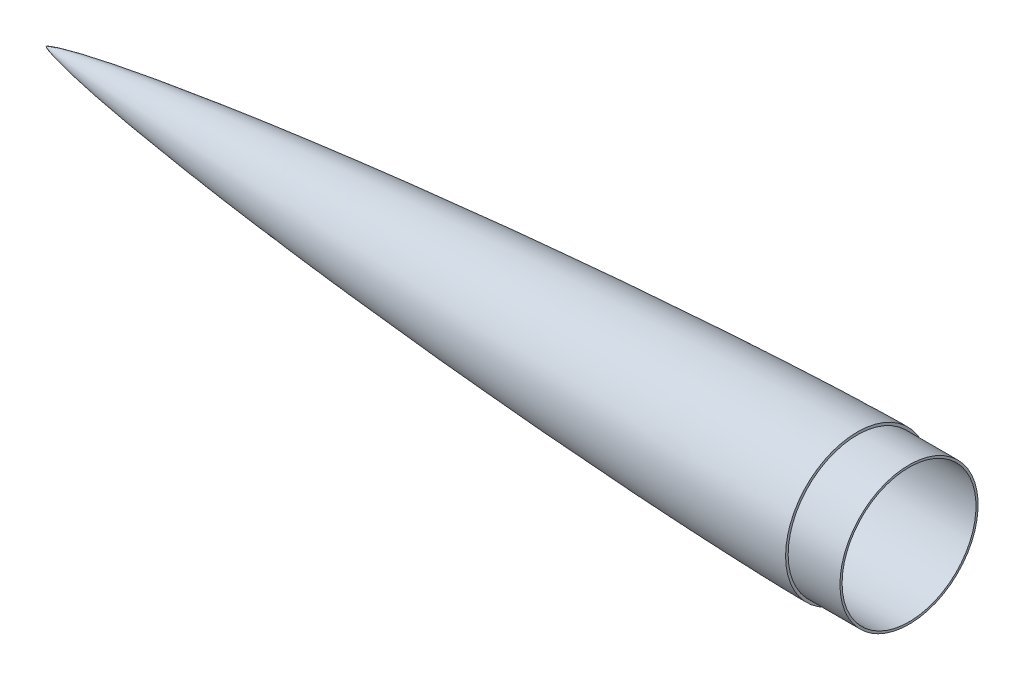
SolidWorks part; units mm, degrees
material "Hexcel AS4C (3000 Filaments)"
ref_plane "Front Plane" through (0, 0, 0) normal (0, 0, 1) x (1, 0, 0)
ref_plane "Top Plane" through (0, 0, 0) normal (0, 1, 0) x (1, 0, 0)
ref_plane "Right Plane" through (0, 0, 0) normal (1, 0, 0) x (0, 0, -1)
sketch "Sketch1" plane through (0, 0, 0) normal (0, 0, 1) x (1, 0, 0)
  line L0 (0, 0) -> (596.9, 0)
  line L2 (596.9, 0) -> (596.9, 52.7482)
  spline S0 degree 4 poles (0, 0) (0.0024, 0.0056) (0.008, 0.0163) (0.0233, 0.0353) (0.0583, 0.069) (0.1105, 0.1106) (0.1804, 0.1587) (0.2798, 0.2202) (0.3991, 0.287) (0.5391, 0.3592) (0.6997, 0.4363) (0.9322, 0.5415) (1.293, 0.6933) (1.9132, 0.9318) (3.0286, 1.3168) (5.0297, 1.9288) (8.7193, 2.9162) (15.6155, 4.5123) (27.7821, 6.9272) (48.0381, 10.379) (75.5616, 14.4184) (108.703, 18.7111) (145.1674, 22.9502) (181.6719, 26.826) (218.2071, 30.3992) (254.767, 33.7085) (291.348, 36.7768) (327.9472, 39.6184) (364.5629, 42.24) (401.1936, 44.6421) (437.8384, 46.8187) (474.4967, 48.7564) (506.5841, 50.2205) (534.0958, 51.2823) (556.2771, 51.9856) (571.2063, 52.3703) (583.4683, 52.6116) (591.1434, 52.712) (594.9811, 52.744) (596.9, 52.7482) knots 0 0 0 0 0 0.00004 0.000081 0.000162 0.000323 0.000485 0.000646 0.00094 0.001234 0.001534 0.001834 0.002641 0.003843 0.005963 0.009698 0.016588 0.029299 0.05314 0.092371 0.153547 0.214723 0.275899 0.337075 0.398251 0.459427 0.520603 0.581779 0.642954 0.70413 0.765306 0.826482 0.887658 0.918246 0.948834 0.974417 0.987208 1 1 1 1 1 construction
  spline S1 degree 4 poles (0, 0) (0.0024, 0.0056) (0.008, 0.0163) (0.0233, 0.0353) (0.0583, 0.069) (0.1105, 0.1106) (0.1804, 0.1587) (0.2798, 0.2202) (0.3991, 0.287) (0.5391, 0.3592) (0.6997, 0.4363) (0.9322, 0.5415) (1.293, 0.6933) (1.9132, 0.9318) (3.0286, 1.3168) (5.0297, 1.9288) (8.7193, 2.9162) (15.6155, 4.5123) (27.7821, 6.9272) (48.0381, 10.379) (75.5616, 14.4184) (108.703, 18.7111) (145.1674, 22.9502) (181.6719, 26.826) (218.2071, 30.3992) (254.767, 33.7085) (291.348, 36.7768) (327.9472, 39.6184) (364.5629, 42.24) (401.1936, 44.6421) (437.8384, 46.8187) (474.4967, 48.7564) (506.5841, 50.2205) (534.0958, 51.2823) (556.2771, 51.9856) (571.2063, 52.3703) (583.4683, 52.6116) (591.1434, 52.712) (594.9811, 52.744) (596.9, 52.7482) knots 0 0 0 0 0 0.00004 0.000081 0.000162 0.000323 0.000485 0.000646 0.00094 0.001234 0.001534 0.001834 0.002641 0.003843 0.005963 0.009698 0.016588 0.029299 0.05314 0.092371 0.153547 0.214723 0.275899 0.337075 0.398251 0.459427 0.520603 0.581779 0.642954 0.70413 0.765306 0.826482 0.887658 0.918246 0.948834 0.974417 0.987208 1 1 1 1 1
  dimension "D1" = 596.9
revolve "Revolve1" add sketch "Sketch1" angle 360 about L0
shell "Shell1" thickness 1.9101 removed face at (596.9, 0, 52.7482)
ref_plane "Shoulder Plane" through (558.8, 0, 0) normal (1, 0, 0) x (0, 0, -1)
sketch "Sketch2" plane through (558.8, 0, 0) normal (1, 0, 0) x (0, 0, -1)
  circle A0 centre (0, 0) radius 49.2506
  circle A1 centre (0, 0) radius 50.8381
  circle A2 centre (0, 0) radius 50.8381
  dimension "D2" = 1.5875
  dimension "D1" = 0
extrude "Boss-Extrude1" add sketch "Sketch2" along normal blind 76.2
